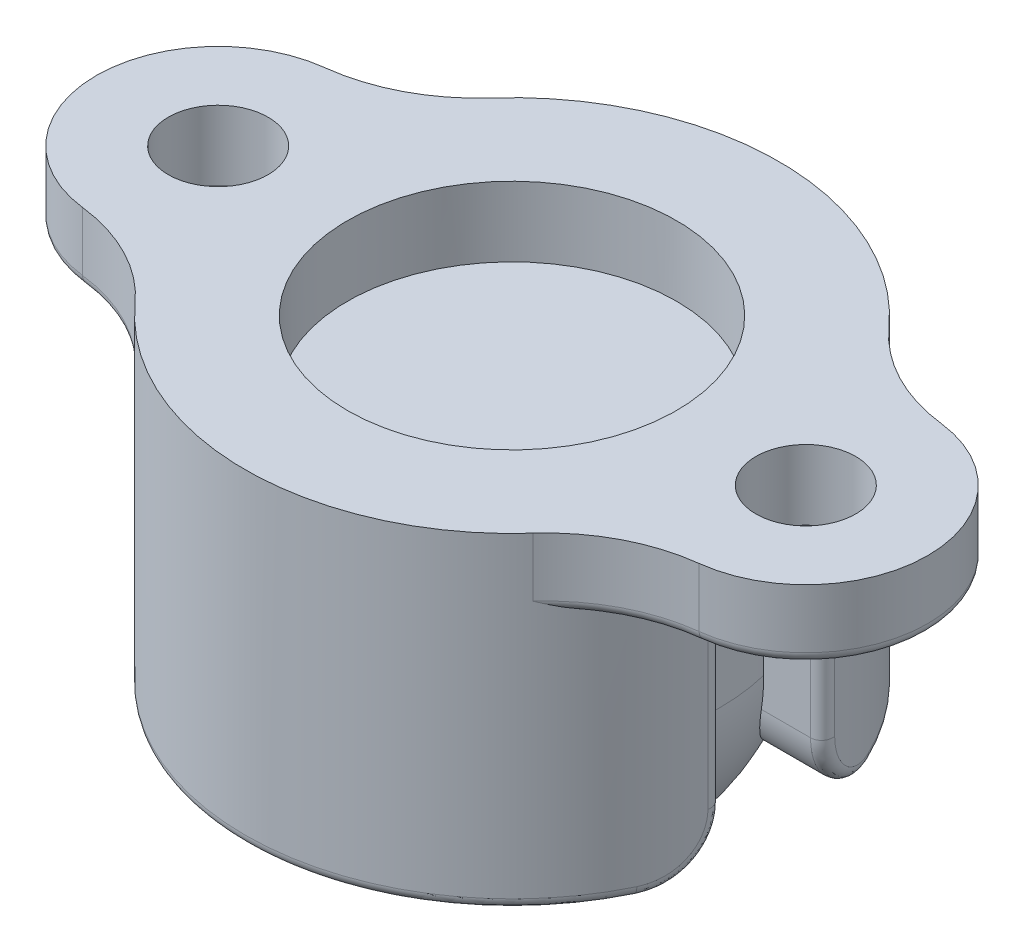
SolidWorks part; units mm, degrees
ref_plane "Front Plane" through (0, 0, 0) normal (0, 0, 1) x (1, 0, 0)
ref_plane "Top Plane" through (0, 0, 0) normal (0, 1, 0) x (1, 0, 0)
ref_plane "Right Plane" through (0, 0, 0) normal (1, 0, 0) x (0, 0, -1)
sketch "Sketch1" plane through (0, 0, 0) normal (0, 1, 0) x (1, 0, 0)
  circle A0 centre (0, 0) radius 6.115
  dimension "D1" = 12.23
extrude "Boss-Extrude1" add sketch "Sketch1" against normal blind 7.5
sketch "Sketch2" plane through (0, 0, 0) normal (0, 1, 0) x (1, 0, 0)
  circle A0 centre (6.731, 0) radius 2.794
  dimension "D1" = 5.588
  dimension "D2" = 6.731
extrude "Boss-Extrude2" add sketch "Sketch2" against normal blind 1.6
sketch "Sketch3" plane through (0, 0, 0) normal (0, 1, 0) x (1, 0, 0)
  circle A0 centre (0, 0) radius 3.77
  dimension "D1" = 7.54
extrude "Cut-Extrude1" cut sketch "Sketch3" against normal blind 1.6
sketch "Sketch4" plane through (0, 0, 0) normal (0, 1, 0) x (1, 0, 0)
  circle A0 centre (6.731, 0) radius 1.143
  dimension "D1" = 2.286
  dimension "D2" = 6.731
extrude "Cut-Extrude2" cut sketch "Sketch4" against normal through all
sketch "Sketch5" plane through (0, -7.5, 0) normal (0, -1, 0) x (1, 0, 0)
  circle A0 centre (0, 0) radius 4.7498
extrude "Cut-Extrude3" cut sketch "Sketch5" against normal blind 5.9
sketch "Sketch6" plane through (0, -7.5, 0) normal (0, -1, 0) x (1, 0, 0)
  line L1 (-6.7312, -1.143) -> (6.7312, -1.143)
  line L2 (-6.7312, -1.143) -> (-6.7312, 1.143)
  line L3 (-6.7312, 1.143) -> (6.7312, 1.143)
  line L4 (6.7312, -1.143) -> (6.7312, 1.143)
  line L5 (-6.7312, -1.143) -> (6.7312, 1.143) construction
  line L6 (-6.7312, 1.143) -> (6.7312, -1.143) construction
  arc A0 (6.0461, -0.9151) -> (6.0461, 0.9151) centre (6.731, 0) ccw construction
  point P0 (0, 0)
extrude "Cut-Extrude4" cut sketch "Sketch6" against normal blind 5.9
mirror "Mirror1" about plane through (0, 0, 0) normal (1, 0, 0) of "Cut-Extrude2", "Boss-Extrude2"
fillet "Fillet1" radius 1.4 4 edges at (-5.3087, -7.5, -1.143) (5.3087, -7.5, -1.143) (5.3087, -7.5, 1.143) (-5.3087, -7.5, 1.143)
fillet "Fillet12" radius 4 4 edges at (-5.5633, -0.8, -2.5383) (5.5633, -0.8, -2.5383) (5.5633, -0.8, 2.5383) (-5.5633, -0.8, 2.5383)
fillet "Fillet3" radius 0.25 6 edges at (9.525, -1.6, 0) (-9.525, -1.6, 0) (5.6904, -1.6, 3.1977) (5.6904, -1.6, -3.1977) (-5.6904, -1.6, 3.1977) (-5.6904, -1.6, -3.1977)
fillet "Fillet11" radius 0.25 10 edges at (-6.0072, -3.85, 1.143) (-5.9437, -6.9588, 1.4374) (6.0072, -3.85, 1.143) (5.8888, -7.1764, 1.6478) (6.0072, -3.85, -1.143) (5.9437, -6.9588, -1.4374) (-6.0072, -3.85, -1.143) (-5.8888, -7.1764, -1.6478) (0, -7.5, 6.115) (0, -7.5, -6.115)
sketch "Sketch8" plane through (0, 0, 0) normal (0, 1, 0) x (1, 0, 0)
  circle A0 centre (0, 0) radius 4.7625
extrude "Boss-Extrude4" add sketch "Sketch8" against normal blind 8.56 from offset 1.6 offset against normal yes
fillet "Fillet9" radius 4.7625 1 edges at (0, -10.16, 4.7625)
